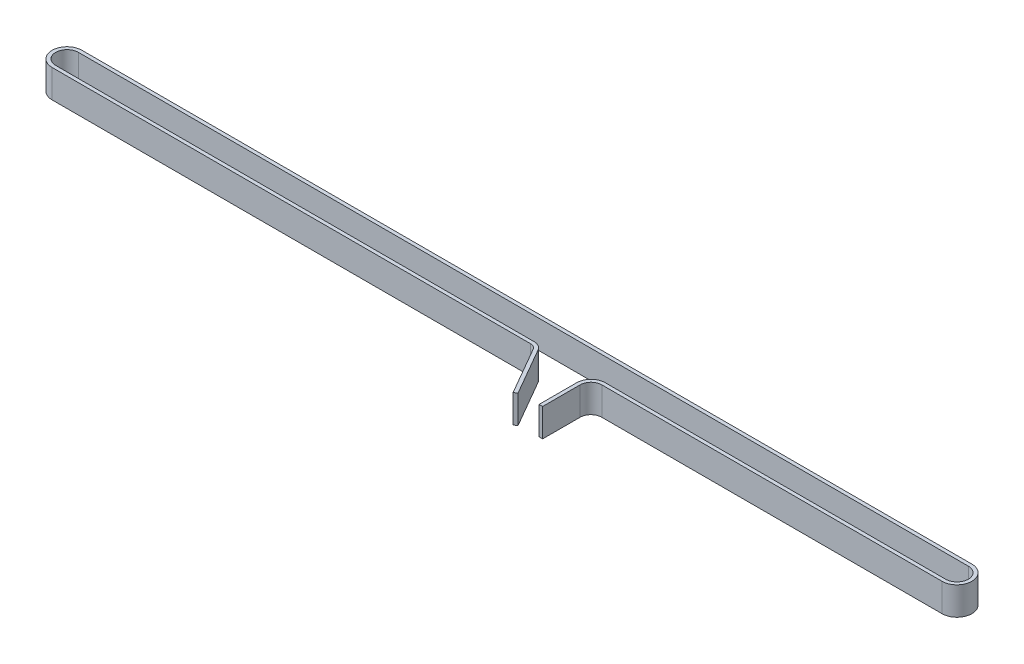
SolidWorks part; units mm, degrees
ref_plane "Front Plane" through (0, 0, 0) normal (0, 0, 1) x (1, 0, 0)
ref_plane "Top Plane" through (0, 0, 0) normal (0, 1, 0) x (1, 0, 0)
ref_plane "Right Plane" through (0, 0, 0) normal (1, 0, 0) x (0, 0, -1)
sketch "Sketch1" plane through (0, 0, 0) normal (0, 1, 0) x (1, 0, 0)
  line L0 (0, 6.365) -> (380, 6.365)
  line L1 (0, -6.365) -> (204.305, -6.365)
  line L2 (206.9031, -7.865) -> (218.6031, -28.13)
  line L3 (380, -6.365) -> (234.695, -6.365)
  line L4 (230.076, -10.984) -> (230.076, -26.984)
  line L5 (234.695, -6.365) -> (204.305, -6.365) construction
  arc A0 (0, 6.365) -> (0, -6.365) centre (0, 0) ccw
  arc A1 (380, -6.365) -> (380, 6.365) centre (380, 0) ccw
  arc A2 (234.695, -6.365) -> (230.076, -10.984) centre (234.695, -10.984) ccw
  arc A3 (204.305, -6.365) -> (206.9031, -7.865) centre (204.305, -9.365) cw
  point P12 (230.076, -6.365)
  point P16 (206.0371, -6.365)
  point P17 (171.8846, -6.365)
  point P18 (0, 0)
  point P19 (222.6561, -6.365)
  point P20 (190, 6.365)
  point P21 (219.5, -6.365)
  dimension "D1" = 380
  dimension "D2" = 12.73
  dimension "D4" = 4.619
  dimension "D6" = 3
  dimension "D3" = 16
  dimension "D5" = 120
  dimension "D7" = 23.4
  dimension "D8" = 30.39
  dimension "D9" = 29.5
extrude "Extrude-Thin1" add sketch "Sketch1" along normal blind 12 thin thin type one direction wall 1.52
